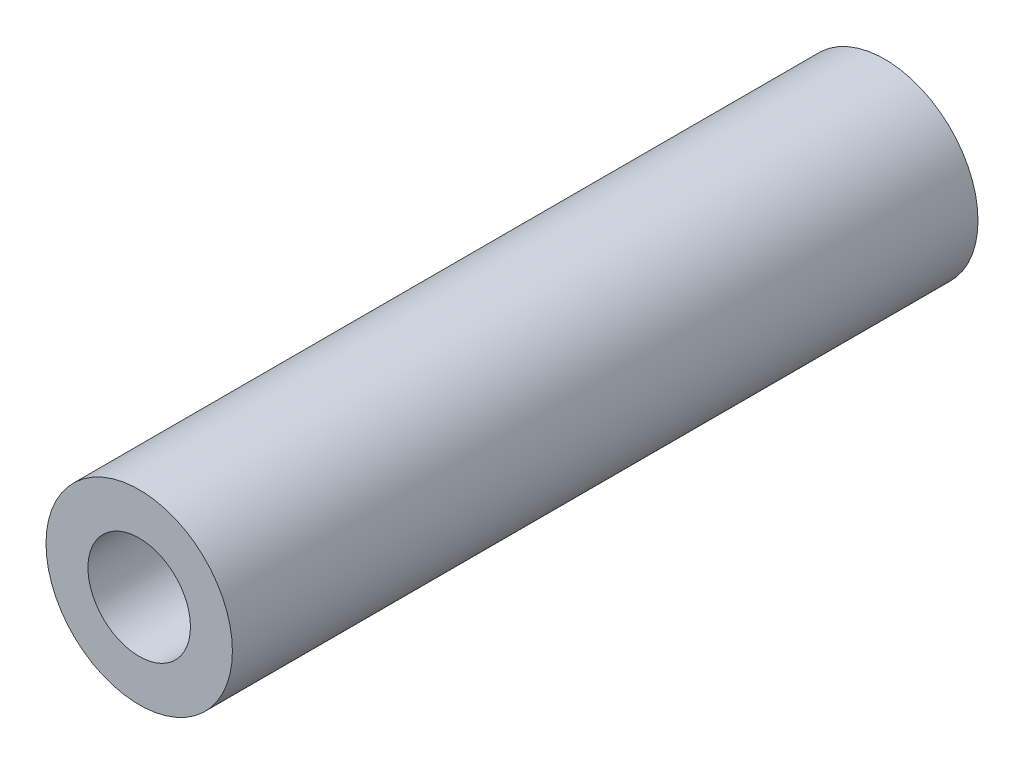
SolidWorks part; units mm, degrees
ref_plane "Płaszczyzna przednia" through (0, 0, 0) normal (0, 0, 1) x (1, 0, 0)
ref_plane "Płaszczyzna górna" through (0, 0, 0) normal (0, 1, 0) x (1, 0, 0)
ref_plane "Płaszczyzna prawa" through (0, 0, 0) normal (1, 0, 0) x (0, 0, -1)
sketch "Szkic1" plane through (0, 0, 0) normal (1, 0, 0) x (0, 0, -1)
  line L0 (-120, 0) -> (-120, 15)
  line L1 (-120, 15) -> (0, 15)
  line L2 (0, 15) -> (0, 0)
  line L3 (0, 0) -> (-120, 0)
  line L4 (0, 0) -> (-120, 0) construction
sketch "Szkic2" plane through (0, 0, 0) normal (1, 0, 0) x (0, 0, -1)
  line L0 (-120, 0) -> (-120, 8.25)
  line L1 (-120, 8.25) -> (0, 8.25)
  line L2 (0, 8.25) -> (0, 0)
  line L3 (0, 0) -> (-120, 0)
  line L4 (0, 0) -> (-120, 0) construction
revolve "Obrót1" add sketch "Szkic1" angle 360 about L4 reverse direction yes
revolve "Wycięcie-obrót1" cut sketch "Szkic2" angle 360 about L4 reverse direction yes
ref_plane "Płaszczyzna1" through (0, 0, 120) normal (0, 0, 1) x (1, 0, 0)
ref_plane "IP2 XY" through (0, 0, 120) normal (0, 0, 1) x (1, 0, 0)
ref_plane "IP2 XZ" through (0, 0, 0) normal (0, -1, 0) x (-1, 0, 0)
ref_plane "IP2 YZ" through (0, 0, 0) normal (1, 0, 0) x (0, 0, -1)
ref_axis "IP2 X" through (-80.9, 0, 120) along (1, 0, 0)
ref_axis "IP2 Y" through (0, -50, 120) along (0, 1, 0)
ref_axis "IP2 Z" through (0, 0, 80.9) along (0, 0, -1)
sketch3d "IP2"
  point P0 (0, 0, 120)
ref_plane "IP1 XY" through (0, 0, 0) normal (0, 0, 1) x (1, 0, 0)
ref_plane "IP1 XZ" through (0, 0, 0) normal (0, -1, 0) x (-1, 0, 0)
ref_plane "IP1 YZ" through (0, 0, 0) normal (1, 0, 0) x (0, 0, -1)
ref_axis "IP1 X" through (-80.9, 0, 0) along (1, 0, 0)
ref_axis "IP1 Y" through (0, -50, 0) along (0, 1, 0)
ref_axis "IP1 Z" through (0, 0, 80.9) along (0, 0, -1)
sketch3d "IP1"
  point P0 (0, 0, 0)
